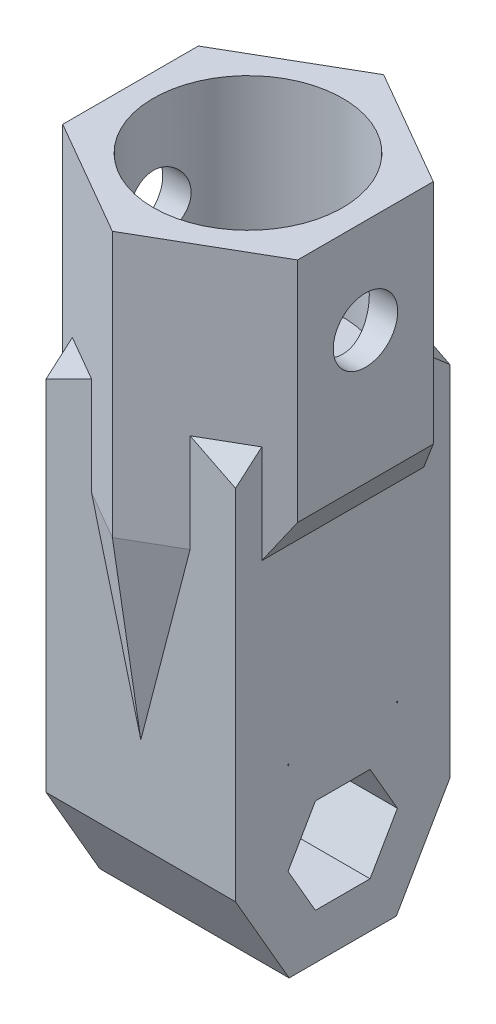
SolidWorks part; units mm, degrees
ref_plane "Alzado" through (0, 0, 0) normal (0, 0, 1) x (1, 0, 0)
ref_plane "Planta" through (0, 0, 0) normal (0, 1, 0) x (1, 0, 0)
ref_plane "Vista lateral" through (0, 0, 0) normal (1, 0, 0) x (0, 0, -1)
sketch "Croquis1" plane through (0, 0, 0) normal (1, 0, 0) x (0, 0, -1)
  line L0 (0, 0) -> (2.8868, 0) construction
  line L1 (2.8868, 0) -> (1.4434, 2.5)
  line L2 (1.4434, 2.5) -> (-1.4434, 2.5)
  line L3 (-1.4434, 2.5) -> (-2.8868, 0)
  line L4 (-2.8868, 0) -> (-1.4434, -2.5)
  line L5 (-1.4434, -2.5) -> (1.4434, -2.5)
  line L6 (1.4434, -2.5) -> (2.8868, 0)
  line L7 (2.829, 4.9) -> (-2.829, 4.9)
  line L8 (-2.829, 4.9) -> (-5.658, 0)
  line L9 (-5.658, 0) -> (-2.829, -4.9)
  line L10 (-2.829, -4.9) -> (2.829, -4.9)
  line L11 (2.829, -4.9) -> (5.658, 0)
  line L12 (5.658, 0) -> (2.829, 4.9)
  circle A0 centre (0, 0) radius 2.5 construction
  point P1 (0, -2.5)
  dimension "D1" = 5
  dimension "D2" = 2.4
extrude "Saliente-Extruir1" add sketch "Croquis1" along normal blind 5 and the other way blind 5
ref_plane "Plano1" through (0, 4.9, 0) normal (0, 1, 0) x (1, 0, 0)
sketch "Croquis2" plane through (0, 4.9, 0) normal (0, 1, 0) x (1, 0, 0)
  line L0 (0, 0) -> (0, 7.1591) construction
  line L1 (0, 7.1591) -> (-6.2, 3.5796)
  line L2 (-6.2, 3.5796) -> (-6.2, -3.5796)
  line L3 (-6.2, -3.5796) -> (0, -7.1591)
  line L4 (0, -7.1591) -> (6.2, -3.5796)
  line L5 (6.2, -3.5796) -> (6.2, 3.5796)
  line L6 (6.2, 3.5796) -> (0, 7.1591)
  circle A0 centre (0, 0) radius 5
  circle A1 centre (0, 0) radius 6.2 construction
  dimension "D1" = 10
  dimension "D2" = 12.4
extrude "Saliente-Extruir2" add sketch "Croquis2" along normal blind 10 from offset 14 separate body
sketch "Croquis4" plane through (0, 0, 0) normal (0, 1, 0) x (1, 0, 0)
  line L1 (-5, -5.658) -> (5, -5.658)
  line L2 (-5, -5.658) -> (-5, -2.8868)
  line L3 (-5, -2.8868) -> (5, -2.8868)
  line L4 (5, -5.658) -> (5, -2.8868)
  line L5 (5, 2.8868) -> (-5, 2.8868)
  line L6 (5, 2.8868) -> (5, 5.658)
  line L7 (5, 5.658) -> (-5, 5.658)
  line L8 (-5, 2.8868) -> (-5, 5.658)
  line L9 (-5, 2.8868) -> (5, 2.8868)
  line L10 (-5, 2.8868) -> (-5, -2.8868)
  line L11 (-5, -2.8868) -> (5, -2.8868)
  line L12 (5, 2.8868) -> (5, -2.8868)
extrude "Saliente-Extruir3" add sketch "Croquis4" along normal up to surface (18.9 mm away) contours L1 L4 L3 L2 | L8 L5 L6 L7 region at (0, 0, 4.2724) region at (0, 0, -4.2724) up to face at (0, 18.9, 0)
chamfer "Chaflán1" distance 1.2 angle 45 4 edges at (3.8, 18.9, 4.9652) (-3.8, 18.9, 4.9652) (-3.8, 18.9, -4.9652) (3.8, 18.9, -4.9652)
ref_plane "Plano2" through (6.2, 0, 0) normal (1, 0, 0) x (0, 0, -1)
sketch "Croquis5" plane through (6.2, 0, 0) normal (1, 0, 0) x (0, 0, -1)
  line L0 (3.5796, 28.9) -> (0, 28.9) construction
  line L1 (-3.5796, 28.9) -> (3.5796, 28.9) construction
  line L2 (0, 28.9) -> (0, 23.9) construction
  circle A0 centre (0, 23.9) radius 1.7
  dimension "D2" = 3.4
  dimension "D1" = 5
extrude "Cortar-Extruir1" cut sketch "Croquis5" against normal through all
extrude "Saliente-Extruir8" add sketch "Croquis2<4>" along normal blind 14 contours L5 L6 L1 L2 L3 L4 A0 | A0 region at (3.0053, 4.9, -5.2053) region at (0, 4.9, 0)
sketch "Croquis2<4>" plane through (0, 4.9, 0) normal (0, 1, 0) x (1, 0, 0) same geometry as "Croquis2"
chamfer "Chaflán2" distance 1.3 distance2 10 4 edges at (-1.3, 4.9, 6.4086) (1.3, 4.9, 6.4086) (-1.3, 4.9, -6.4086) (1.3, 4.9, -6.4086) first distance on face at (0, 4.9, 6.1584) first distance on face at (0, 4.9, -6.1584)
sketch "Croquis6" plane through (0, 0, 0) normal (0, 0, 1) x (1, 0, 0)
  line L0 (2.6, 14.9) -> (5, 14.9) construction
  line L1 (5, 18.9) -> (5, 0) construction
  line L2 (5, 14.9) -> (6.2, 16.9)
  line L3 (6.2, 28.9) -> (6.2, 4.9) construction
  line L4 (6.2, 16.9) -> (6.2, 4.9)
  line L5 (6.2, 4.9) -> (5, 4.9)
  line L6 (5, 4.9) -> (5, 14.9)
  line L7 (0, 14.9) -> (0, 0) construction
  line L8 (0, 28.9) -> (0, 14.9) construction
  line L9 (-6.2, 4.9) -> (-5, 4.9)
  line L10 (-6.2, 16.9) -> (-6.2, 4.9)
  line L11 (-5, 14.9) -> (-6.2, 16.9)
  line L12 (-5, 4.9) -> (-5, 14.9)
  point P17 (0, 14.9)
extrude "Cortar-Extruir2" cut sketch "Croquis6" against normal through all both and the other way through all
